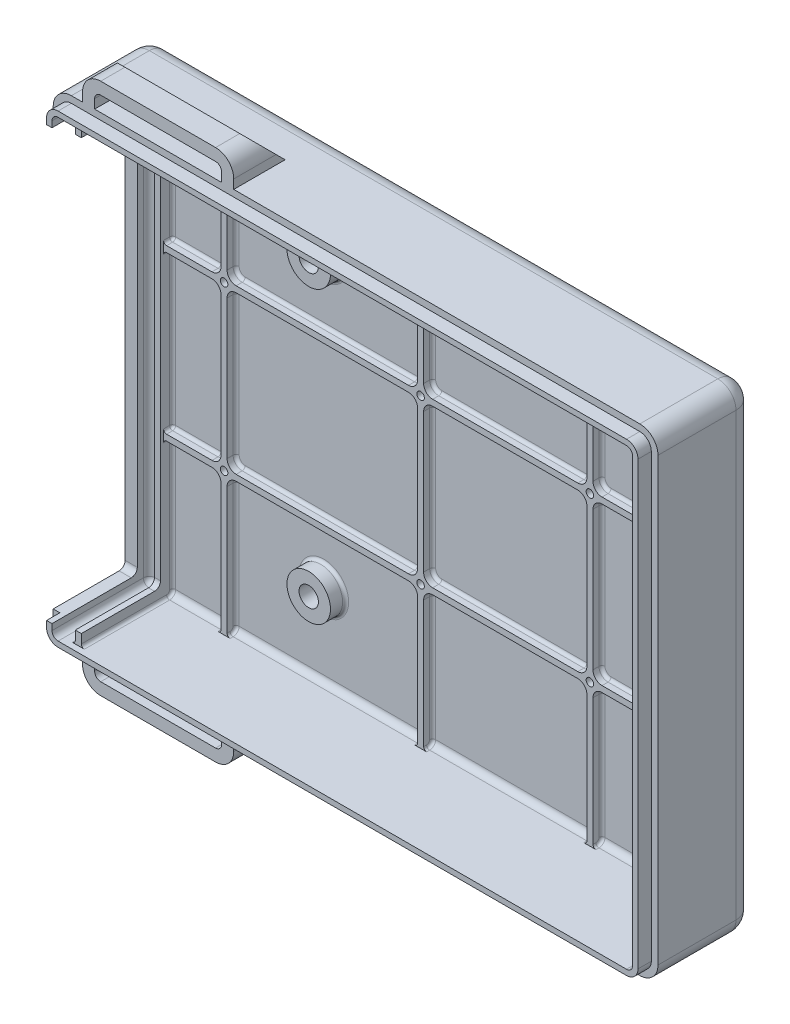
SolidWorks part; units mm, degrees
ref_plane "前视基准面" through (0, 0, 0) normal (0, 0, 1) x (1, 0, 0)
ref_plane "上视基准面" through (0, 0, 0) normal (0, 1, 0) x (1, 0, 0)
ref_plane "右视基准面" through (0, 0, 0) normal (1, 0, 0) x (0, 0, -1)
sketch "草图1" plane through (0, 0, 0) normal (0, 0, 1) x (1, 0, 0)
  line L1 (0, 0) -> (96, 0)
  line L2 (0, 0) -> (0, 75)
  line L3 (0, 75) -> (96, 75)
  line L4 (96, 0) -> (96, 75)
  dimension "D1" = 96
  dimension "D2" = 75
extrude "凸台-拉伸1" add sketch "草图1" along normal blind 2
sketch "草图2" plane through (0, 0, 0) normal (0, 0, 1) x (1, 0, 0)
  line L20 (-2, 77) -> (98, 77)
  line L21 (-2, 77) -> (-2, -2)
  line L22 (-2, -2) -> (98, -2)
  line L23 (98, 77) -> (98, -2)
  line L24 (0, 75) -> (96, 75)
  line L25 (0, 75) -> (0, 0)
  line L26 (0, 0) -> (96, 0)
  line L27 (96, 75) -> (96, 0)
  dimension "D1" = 2
  dimension "D2" = 2
  dimension "D3" = 2
  dimension "D4" = 2
extrude "凸台-拉伸2" add sketch "草图2" along normal blind 18.1
sketch "草图3" plane through (0, 0, 18.1) normal (0, 0, 1) x (1, 0, 0)
  line L0 (0, 0) -> (96, 0) construction
  line L1 (-0.9, 75.9) -> (96.9, 75.9)
  line L2 (-0.9, 75.9) -> (-0.9, -0.9)
  line L3 (-0.9, -0.9) -> (96.9, -0.9)
  line L4 (96.9, 75.9) -> (96.9, -0.9)
  line L5 (-2, 77) -> (98, 77)
  line L6 (-2, 77) -> (-2, -2)
  line L7 (-2, -2) -> (98, -2)
  line L8 (98, 77) -> (98, -2)
  line L9 (96, 0) -> (96, 75) construction
  line L10 (96, 75) -> (0, 75) construction
  line L11 (0, 75) -> (0, 0) construction
  dimension "D1" = 0.9
  dimension "D2" = 0.9
  dimension "D3" = 0.9
  dimension "D4" = 0.9
extrude "切除-拉伸1" cut sketch "草图3" against normal blind 2.2
fillet "圆角1" radius 1 8 edges at (96, 0, 10.05) (48, 0, 2) (96, 37.5, 2) (48, 75, 2) (96, 75, 10.05) (0, 0, 10.05) (0, 75, 10.05) (0, 37.5, 2)
fillet "圆角2" radius 3 8 edges at (98, -2, 7.95) (48, -2, 0) (48, 77, 0) (98, 37.5, 0) (98, 77, 7.95) (-2, 77, 7.95) (-2, -2, 7.95) (-2, 37.5, 0)
fillet "圆角5" radius 1.9 4 edges at (96.9, -0.9, 17) (96.9, 75.9, 17) (-0.9, 75.9, 17) (-0.9, -0.9, 17)
sketch "草图4" plane through (0, 0, 2) normal (0, 0, 1) x (1, 0, 0)
  line L0 (1, 0) -> (95, 0) construction
  line L1 (48, 75) -> (48, 0) construction
  line L2 (0, 75) -> (96, 75) construction
  line L3 (0, 0) -> (96, 0) construction
  point P0 (3.85, 5)
  point P7 (2.85, 5)
  point P11 (48, 37.5)
  dimension "D1" = 3.85
  dimension "D2" = 5
  dimension "D3" = 2.85
  dimension "D4" = 5
ref_plane "基准面1" through (3.85, 0, 0) normal (1, 0, 0) x (0, 0, -1)
ref_plane "基准面2" through (0, 5, 0) normal (0, 1, 0) x (1, 0, 0)
sketch "草图8" plane through (3.85, 0, 0) normal (1, 0, 0) x (0, 0, -1)
  line L0 (8.305, 5) -> (-8.305, 5) construction
  point P0 (-4.5, 5)
  dimension "D1" = 2.5
ref_plane "基准面3" through (0, 0, 4.5) normal (0, 0, 1) x (1, 0, 0)
ref_plane "基准面4" through (2.85, 0, 0) normal (1, 0, 0) x (0, 0, -1)
sketch "草图11" plane through (2.85, 0, 0) normal (1, 0, 0) x (0, 0, -1)
  line L0 (0, 0) -> (0, 75) construction
  line L1 (-17.1, 75) -> (-2, 75)
  line L2 (-17.1, 75) -> (-17.1, 0)
  line L3 (-17.1, 0) -> (-2, 0)
  line L4 (-2, 75) -> (-2, 0)
  line L5 (-15.9, -2) -> (-3, -2) construction
  line L7 (-3, 77) -> (-15.9, 77) construction
  dimension "D2" = 2
  dimension "D3" = 2
  dimension "D4" = 15.1
extrude "凸台-拉伸3" add sketch "草图11" along normal blind 1
sketch "草图9" plane through (0, 0, 0) normal (1, 0, 0) x (0, 0, -1)
  line L0 (-18.1, 75) -> (-3, 75) construction
  line L1 (-4, 73) -> (-18.1, 73)
  line L2 (-4, 73) -> (-4, 2)
  line L3 (-4, 2) -> (-18.1, 2)
  line L4 (-18.1, 73) -> (-18.1, 2)
  line L5 (-3, 0) -> (-18.1, 0) construction
  dimension "D1" = 2
  dimension "D2" = 2
  dimension "D3" = 2
  dimension "D4" = 14.1
extrude "切除-拉伸3" cut sketch "草图9" against normal through all and the other way up to surface (3.85 mm away) other way up to face at (3.85, 37.5, 7.2976)
fillet "圆角8" radius 1 4 edges at (-1, 2, 4) (3.35, 2, 4) (3.35, 73, 4) (-1, 73, 4)
fillet "圆角9" radius 0.5 10 edges at (2.85, 0, 10.05) (2.85, 0.2929, 2.2929) (2.85, 37.5, 2) (2.85, 74.7071, 2.2929) (3.85, 0, 10.05) (3.85, 0.2929, 2.2929) (3.85, 37.5, 2) (3.85, 74.7071, 2.2929) (2.85, 75, 10.05) (3.85, 75, 10.05)
sketch "草图14" plane through (0, 0, 2) normal (0, 0, 1) x (1, 0, 0)
  circle A0 centre (90.85, 13.5) radius 3.4
  circle A1 centre (90.85, 61.5) radius 3.4
  circle A2 centre (28.85, 13.5) radius 3.6
  circle A3 centre (28.85, 61.5) radius 3.6
  dimension "D1" = 6.8
  dimension "D2" = 6.8
  dimension "D7" = 7.2
  dimension "D8" = 7.2
  dimension "D3" = 88
  dimension "D4" = 56.5
  dimension "D5" = 88
  dimension "D6" = 8.5
  dimension "D9" = 26
  dimension "D10" = 8.5
  dimension "D11" = 26
  dimension "D12" = 56.5
extrude "凸台-拉伸4" add sketch "草图14" along normal blind 2.5
sketch "草图15" plane through (0, 0, 4.5) normal (0, 0, 1) x (1, 0, 0)
  circle A0 centre (28.85, 61.5) radius 1.6
  circle A1 centre (28.85, 13.5) radius 1.6
  dimension "D1" = 3.2
  dimension "D2" = 3.2
extrude "切除-拉伸4" cut sketch "草图15" against normal through all
sketch "草图16" plane through (0, 0, 4.5) normal (0, 0, 1) x (1, 0, 0)
  circle A0 centre (90.85, 61.5) radius 1.6
  circle A1 centre (90.85, 13.5) radius 1.6
  dimension "D1" = 3.2
  dimension "D2" = 3.2
extrude "切除-拉伸5" cut sketch "草图16" against normal through all
fillet "圆角10" radius 0.5 4 edges at (25.25, 13.5, 2) (25.25, 61.5, 2) (87.45, 13.5, 2) (87.45, 61.5, 2)
chamfer "倒角2" distance 1.5 angle 45 4 edges at (30.45, 13.5, 0) (30.45, 61.5, 0) (92.45, 61.5, 0) (92.45, 13.5, 0)
sketch "草图17" plane through (0, 0, 2) normal (0, 0, 1) x (1, 0, 0)
  line L0 (3.85, -8.305) -> (3.85, 8.305) construction
  line L1 (3.85, 51) -> (13.35, 51)
  line L2 (3.85, 51) -> (3.85, 50)
  line L3 (3.85, 50) -> (13.35, 50)
  line L4 (96, 51) -> (96, 50)
  line L5 (96, 0) -> (96, 75) construction
  line L6 (0, 75) -> (96, 75) construction
  line L7 (13.35, 75) -> (14.35, 75)
  line L8 (13.35, 75) -> (13.35, 51)
  line L9 (13.35, 0) -> (14.35, 0)
  line L10 (14.35, 75) -> (14.35, 51)
  line L11 (0, 0) -> (96, 0) construction
  line L12 (14.35, 51) -> (45.85, 51)
  line L13 (45.85, 75) -> (46.85, 75)
  line L14 (45.85, 75) -> (45.85, 51)
  line L15 (45.85, 0) -> (46.85, 0)
  line L16 (46.85, 75) -> (46.85, 51)
  line L17 (73.85, 75) -> (74.85, 75)
  line L18 (73.85, 75) -> (73.85, 51)
  line L19 (73.85, 0) -> (74.85, 0)
  line L20 (74.85, 75) -> (74.85, 51)
  line L21 (3.85, 24) -> (13.35, 24)
  line L22 (3.85, 24) -> (3.85, 23)
  line L23 (3.85, 23) -> (13.35, 23)
  line L24 (96, 24) -> (96, 23)
  line L25 (14.35, 50) -> (45.85, 50)
  line L26 (14.35, 50) -> (14.35, 24)
  line L27 (13.35, 50) -> (13.35, 24)
  line L28 (46.85, 51) -> (73.85, 51)
  line L29 (46.85, 50) -> (73.85, 50)
  line L30 (46.85, 50) -> (46.85, 24)
  line L31 (45.85, 50) -> (45.85, 24)
  line L32 (74.85, 51) -> (96, 51)
  line L33 (74.85, 50) -> (96, 50)
  line L34 (73.85, 50) -> (73.85, 24)
  line L35 (74.85, 24) -> (96, 24)
  line L36 (74.85, 23) -> (96, 23)
  line L37 (74.85, 23) -> (74.85, 0)
  line L38 (73.85, 23) -> (73.85, 0)
  line L39 (46.85, 24) -> (73.85, 24)
  line L40 (46.85, 23) -> (73.85, 23)
  line L41 (46.85, 23) -> (46.85, 0)
  line L42 (45.85, 23) -> (45.85, 0)
  line L43 (14.35, 24) -> (45.85, 24)
  line L44 (14.35, 23) -> (45.85, 23)
  line L45 (14.35, 23) -> (14.35, 0)
  line L46 (13.35, 23) -> (13.35, 0)
  line L47 (74.85, 50) -> (74.85, 24)
  dimension "D6" = 24
  dimension "D7" = 23
  dimension "D8" = 9.5
  dimension "D9" = 42
  dimension "D10" = 70
extrude "凸台-拉伸5" add sketch "草图17" along normal blind 1.5
fillet "圆角11" radius 1.5 24 edges at (74.85, 23, 2.75) (73.85, 23, 2.75) (46.85, 23, 2.75) (45.85, 23, 2.75) (13.35, 23, 2.75) (14.35, 23, 2.75) (13.35, 51, 2.75) (73.85, 51, 2.75) (74.85, 51, 2.75) (46.85, 51, 2.75) (45.85, 51, 2.75) (14.35, 51, 2.75) (13.35, 24, 2.75) (13.35, 50, 2.75) (74.85, 24, 2.75) (74.85, 50, 2.75) (73.85, 24, 2.75) (73.85, 50, 2.75) (46.85, 24, 2.75) (46.85, 50, 2.75) (45.85, 24, 2.75) (45.85, 50, 2.75) (14.35, 24, 2.75) (14.35, 50, 2.75)
sketch "草图18" plane through (0, 0, 3.5) normal (0, 0, 1) x (1, 0, 0)
  line L0 (11.85, 50) -> (15.85, 51) construction
  line L1 (44.35, 50) -> (48.35, 51) construction
  line L2 (72.35, 50) -> (76.35, 51) construction
  line L3 (11.85, 23) -> (15.85, 24) construction
  line L4 (44.35, 23) -> (48.35, 24) construction
  line L5 (72.35, 23) -> (76.35, 24) construction
  arc A0 (45.85, 48.5) -> (44.35, 50) centre (44.35, 48.5) ccw construction
  arc A1 (13.35, 21.5) -> (11.85, 23) centre (11.85, 21.5) ccw construction
  arc A2 (13.35, 21.5) -> (11.85, 23) centre (11.85, 21.5) ccw construction
  arc A3 (73.85, 21.5) -> (72.35, 23) centre (72.35, 21.5) ccw construction
  arc A4 (73.85, 21.5) -> (72.35, 23) centre (72.35, 21.5) ccw construction
  circle A5 centre (13.85, 50.5) radius 0.625
  circle A6 centre (46.35, 50.5) radius 0.625
  circle A7 centre (74.35, 50.5) radius 0.625
  circle A8 centre (74.35, 23.5) radius 0.625
  circle A9 centre (46.35, 23.5) radius 0.625
  circle A10 centre (13.85, 23.5) radius 0.625
  dimension "D1" = 1.25
  dimension "D2" = 1.25
  dimension "D3" = 1.25
  dimension "D4" = 1.25
  dimension "D5" = 1.25
  dimension "D6" = 1.25
extrude "切除-拉伸6" cut sketch "草图18" against normal blind 1.5
fillet "圆角12" radius 0.5 104 edges at (74.85, 0, 3.25) (74.85, 0.2929, 2.2929) (96, 23, 3.25) (95.7071, 23, 2.2929) (85.675, 23, 2) (75.2893, 22.5607, 2) (46.85, 0, 3.25) (46.85, 0.2929, 2.2929) (46.85, 11.25, 2) (47.2893, 22.5607, 2) (73.85, 0, 3.25) (73.85, 0.2929, 2.2929) (73.85, 11.25, 2) (73.4107, 22.5607, 2) (14.35, 0, 3.25) (14.35, 0.2929, 2.2929) (14.35, 11.25, 2) (14.7893, 22.5607, 2) (45.85, 0, 3.25) (45.85, 0.2929, 2.2929) (45.85, 11.25, 2) (45.4107, 22.5607, 2) (3.85, 23, 3) (3.9964, 23, 2.1464) (13.35, 0, 3.25) (13.35, 0.2929, 2.2929) (13.35, 11.25, 2) (12.9107, 22.5607, 2) (96, 24, 3.25) (95.7071, 24, 2.2929) (85.675, 24, 2) (75.2893, 24.4393, 2) (74.85, 37, 2) (75.2893, 49.5607, 2) (96, 50, 3.25) (95.7071, 50, 2.2929) (96, 51, 3.25) (95.7071, 51, 2.2929) (85.675, 51, 2) (75.2893, 51.4393, 2) (74.85, 75, 3.25) (74.85, 74.7071, 2.2929) (60.35, 50, 2) (73.4107, 49.5607, 2) (73.85, 37, 2) (73.4107, 24.4393, 2) (60.35, 24, 2) (47.2893, 24.4393, 2) (46.85, 37, 2) (73.85, 75, 3.25) (73.85, 74.7071, 2.2929) (73.85, 63.25, 2) (73.4107, 51.4393, 2) (60.35, 51, 2) (47.2893, 51.4393, 2) (46.85, 75, 3.25) (46.85, 74.7071, 2.2929) (45.4107, 49.5607, 2) (45.85, 37, 2) (45.4107, 24.4393, 2) (30.1, 24, 2) (14.7893, 24.4393, 2) (14.35, 37, 2) (14.7893, 49.5607, 2) (3.85, 50, 3) (3.9964, 50, 2.1464) (3.85, 24, 3) (3.9964, 24, 2.1464) (8.1, 24, 2) (12.9107, 24.4393, 2) (13.35, 37, 2) (12.9107, 49.5607, 2) (13.35, 75, 3.25) (13.35, 74.7071, 2.2929) (3.85, 51, 3) (3.9964, 51, 2.1464) (8.1, 51, 2) (12.9107, 51.4393, 2) (45.85, 75, 3.25) (45.85, 74.7071, 2.2929) (45.85, 63.25, 2) (45.4107, 51.4393, 2) (30.1, 51, 2) (14.7893, 51.4393, 2) (14.35, 75, 3.25) (14.35, 74.7071, 2.2929) (74.85, 11.25, 2) (60.35, 23, 2) (30.1, 23, 2) (8.1, 23, 2) (85.675, 50, 2) (74.85, 63.25, 2) (47.2893, 49.5607, 2) (46.85, 63.25, 2) (30.1, 50, 2) (8.1, 50, 2) (13.35, 63.25, 2) (14.35, 63.25, 2) (14.475, 50.5, 2) (46.975, 50.5, 2) (74.975, 50.5, 2) (74.975, 23.5, 2) (46.975, 23.5, 2) (14.475, 23.5, 2)
sketch "草图19" plane through (0, 0, 15.9) normal (0, 0, 1) x (1, 0, 0)
  line L0 (95, 77) -> (1, 77) construction
  line L1 (2.85, 77) -> (4.85, 77)
  line L2 (2.85, 77) -> (2.85, 81.5)
  line L3 (2.85, 81.5) -> (27.85, 81.5)
  line L4 (27.85, 77) -> (27.85, 81.5)
  line L5 (2.85, -8.305) -> (2.85, 8.305) construction
  line L7 (4.85, 77) -> (4.85, 79.5)
  line L8 (4.85, 79.5) -> (25.85, 79.5)
  line L9 (25.85, 77) -> (25.85, 79.5)
  line L10 (25.85, 77) -> (27.85, 77)
  dimension "D1" = 21
  dimension "D2" = 2
  dimension "D3" = 2
  dimension "D4" = 2
  dimension "D5" = 2.5
  dimension "D6" = 0
extrude "凸台-拉伸6" add sketch "草图19" against normal blind 4
ref_plane "基准面5" through (0, 37.5, 0) normal (0, -1, 0) x (-1, 0, 0)
mirror "镜向1" about plane through (0, 37.5, 0) normal (0, -1, 0) of "凸台-拉伸6"
chamfer "倒角3" distance 4.5 angle 45 2 edges at (26.85, -2, 11.9) (3.85, 77, 11.9)
fillet "圆角13" radius 1 4 edges at (25.85, 79.5, 12.9) (4.85, 79.5, 12.9) (25.85, -4.5, 12.9) (4.85, -4.5, 12.9)
fillet "圆角14" radius 3 4 edges at (2.85, -6.5, 13.9) (27.85, -6.5, 13.9) (27.85, 81.5, 13.9) (2.85, 81.5, 13.9)
sketch "草图20" plane through (0, 0, 0) normal (0, 0, -1) x (-1, 0, 0)
  line L0 (-8.305, 37.5) -> (8.305, 37.5) construction
  line L1 (-80.9912, 62.75) -> (-50.4912, 62.75)
  line L2 (-80.9912, 62.75) -> (-80.9912, 12.25)
  line L3 (-80.9912, 12.25) -> (-50.4912, 12.25)
  line L4 (-50.4912, 62.75) -> (-50.4912, 12.25)
  line L5 (-80.9912, 62.75) -> (-50.4912, 12.25) construction
  line L6 (-80.9912, 12.25) -> (-50.4912, 62.75) construction
  point P0 (-65.7412, 37.5)
  dimension "D1" = 30.5
  dimension "D2" = 50.5
extrude "切除-拉伸7" cut sketch "草图20" against normal blind 0.3
sketch "草图21" plane through (0, 0, 0) normal (0, 0, -1) x (-1, 0, 0)
  line L0 (0.9219, 74) -> (-95, 1) construction
  line L1 (-1, 74) -> (-95, 74) construction
  line L2 (-48, 75) -> (-48, 0) construction
  line L3 (-93.3155, 3.7445) -> (-2.6845, 3.7445) construction
  line L4 (-93.3155, 3.7445) -> (-93.3155, 71.2555) construction
  line L5 (-93.3155, 71.2555) -> (-2.6845, 71.2555) construction
  line L6 (-2.6845, 3.7445) -> (-2.6845, 71.2555) construction
  line L7 (-93.3155, 3.7445) -> (-2.6845, 71.2555) construction
  line L8 (-93.3155, 71.2555) -> (-2.6845, 3.7445) construction
  circle A0 centre (-93.3155, 71.2555) radius 0.75
  circle A1 centre (-2.6845, 71.2555) radius 0.75
  circle A2 centre (-93.3155, 3.7445) radius 0.75
  circle A3 centre (-2.6845, 3.7445) radius 0.75
  point P5 (-48, 37.5)
  point P6 (-48, 37.5)
  dimension "D1" = 1.5
  dimension "D2" = 1.5
  dimension "D3" = 1.5
  dimension "D4" = 1.5
extrude "凸台-拉伸7" add sketch "草图21" along normal blind 0.75
fillet "圆角15" radius 0.75 4 edges at (92.5655, 3.7445, -0.75) (1.9345, 3.7445, -0.75) (1.9345, 71.2555, -0.75) (92.5655, 71.2555, -0.75)
equation "\"dim.x.base_internal\" = 96"
equation "\"dim.y.base_internal\"= 75"
equation "\"thickness.wall.side\"= 2"
equation "\"thickness.rib\"= \"thickness.wall.side\" * 0.5"
equation "\"thickness.gasset\"= \"thickness.wall.side\" * 0.5"
equation "\"dim.y.xlr1_to_datum\"= 13"
equation "\"dim.y.xlr2_to_datum\"= 40"
equation "\"dim.z.board_to_base\"=2.5"
equation "\"dim.z.board_thickness\"= 1.6"
equation "\"D1@草图1\"=\"dim.x.base_internal\""
equation "\"D2@草图1\"=\"dim.y.base_internal\""
equation "\"D1@凸台-拉伸1\"=\"thickness.wall.side\""
equation "\"dim.z.xlr_opening_to_board\"= 12.5"
equation "\"dim.z.base_internal\"= 16.1"
equation "\"dim.z.base_external\"= \"dim.z.base_internal\" + \"thickness.wall.side\""
equation "\"D1@草图2\"=\"thickness.wall.side\""
equation "\"D2@草图2\"=\"thickness.wall.side\""
equation "\"D3@草图2\"=\"thickness.wall.side\""
equation "\"D4@草图2\"=\"thickness.wall.side\""
equation "\"D1@凸台-拉伸2\"=\"dim.z.base_external\""
equation "\"thickness.mating.side\"= ( \"thickness.wall.side\" / 2 ) - 0.1"
equation "\"D3@草图3\"=\"thickness.mating.side\""
equation "\"D1@草图3\"=\"thickness.mating.side\""
equation "\"D2@草图3\"=\"thickness.mating.side\""
equation "\"D4@草图3\"=\"thickness.mating.side\""
equation "\"dim.cut.mating_cut\"= \"thickness.wall.side\" * 1 + 0.2"
equation "\"D1@切除-拉伸1\"=\"dim.cut.mating_cut\""
equation "\"dim.r.side_internal\"= \"thickness.wall.side\" * 0.5"
equation "\"dim.r.side_external\"= \"thickness.wall.side\" * 1.5"
equation "\"D1@圆角1\"=\"dim.r.side_internal\""
equation "\"D1@圆角2\"=\"dim.r.side_external\""
equation "\"dim.r.mating_side_external\"= \"dim.r.side_internal\" + \"thickness.mating.side\""
equation "\"D1@圆角5\"=\"dim.r.mating_side_external\""
equation "\"mea.x.board_length\"= 65"
equation "\"mea.y.board_width\"= 65"
equation "\"dim.y.board_clearance\"= 5"
equation "\"dim.z.xlr_lower_drill_to_board\"= 2.75"
equation "\"dim.z.xlr_up_drill_to_board\"= \"dim.z.xlr_lower_drill_to_board\" + 19.8"
equation "\"dim.d.xlr_opening\"= 22.2"
equation "\"dim.y.xlr_drill_to_center\"= 19.8 / 2"
equation "\"dim.d.xlr_drill\"= 3.2"
equation "\"dim.y.switch_opening_width\"= 3.3"
equation "\"dim.z.switch_opening_height\"= 7"
equation "\"dim.r.switch_opening_chamfer\"= \"dim.y.switch_opening_width\" / 2"
equation "\"dim.z.switch_opening_to_board\"= 6.66"
equation "\"dim.y.switch_opening_to_datum\"= 58"
equation "\"D2@草图4\"=\"dim.y.board_clearance\""
equation "\"D1@草图8\"=\"dim.z.board_to_base\""
equation "\"dim.y.front_opening_side\"= 2"
equation "\"dim.z.front_opening_bottom\"= 2"
equation "\"D1@草图9\"=\"dim.y.front_opening_side\""
equation "\"D2@草图9\"=\"dim.y.front_opening_side\""
equation "\"D4@草图9\"=\"dim.z.base_internal\"-\"dim.z.front_opening_bottom\""
equation "\"D3@草图9\"=\"dim.z.front_opening_bottom\""
equation "\"dim.x.front_opening_slot\"= 2.85"
equation "\"D3@草图4\"=\"dim.x.front_opening_slot\""
equation "\"D1@草图4\"=\"dim.x.front_opening_slot\"+ \"dim.x.thickness_front_opening_rib\""
equation "\"D1@草图11\"=\"thickness.wall.side\""
equation "\"D2@草图11\"=\"thickness.wall.side\""
equation "\"D3@草图11\"=\"thickness.wall.side\""
equation "\"D4@草图11\"=\"dim.z.base_internal\" - 1"
equation "\"dim.x.thickness_front_opening_rib\"= 1"
equation "\"D1@凸台-拉伸3\"=\"dim.x.thickness_front_opening_rib\""
equation "\"D1@圆角8\"=\"dim.r.side_internal\""
equation "\"D1@圆角9\"=\"dim.r.rib_chamfer\""
equation "\"dim.r.rib_chamfer\"= 0.5"
equation "\"dim.r.gussets_chamfer\"= 0.5"
equation "\"dim.d.boss_short_drill\"=2.8"
equation "\"dim.d.boss_short\"= \"dim.d.boss_short_drill\" + 2 * \"thickness.wall.side\""
equation "\"dim.d.boss_long_drill\"= 2.2"
equation "\"dim.d.boss_long\"= \"dim.d.boss_long_drill\" * 3"
equation "\"dim.z.boss_long_height\"= 20"
equation "\"dim.z.boss_long_depth\"= \"dim.z.boss_long_height\" + 0.35 * \"thickness.wall.side\""
equation "\"dim.r.boss_short\"= 0.5"
equation "\"dim.r.boss_long\"= 1"
equation "\"dim.d.boss_long_chamfer\"= 0.5"
equation "\"D1@草图14\"=\"dim.d.boss_short\""
equation "\"D2@草图14\"=\"dim.d.boss_short\""
equation "\"dim.d.drill_st3\"= 3.20mm"
equation "\"dim.d.boss_short_st\"= \"dim.d.drill_st3\" + 2 * \"thickness.wall.side\""
equation "\"D7@草图14\"=\"dim.d.boss_short_st\""
equation "\"D8@草图14\"=\"dim.d.boss_short_st\""
equation "\"D1@凸台-拉伸4\"=\"dim.z.board_to_base\""
equation "\"D1@草图15\"=\"dim.d.drill_st3\""
equation "\"D2@草图15\"=\"dim.d.drill_st3\""
equation "\"D1@草图16\"=\"dim.d.drill_st3\""
equation "\"D2@草图16\"=\"dim.d.drill_st3\""
equation "\"D1\"= \"dim.z.boss_short_depth\""
equation "\"D1@圆角10\"=\"dim.r.boss_short\""
equation "\"dim.d.chamfer_external_st3\"= 1.5"
equation "\"D1@倒角2\"=\"dim.d.chamfer_external_st3\""
equation "\"dim.d.chamfer_external_m2.5\"= 1.5"
equation "\"D4@草图4\"=\"dim.y.board_clearance\""
equation "\"D1@草图17\"=\"thickness.rib\""
equation "\"D2@草图17\"=\"thickness.rib\""
equation "\"D3@草图17\"=\"thickness.rib\""
equation "\"D4@草图17\"=\"thickness.rib\""
equation "\"D5@草图17\"=\"thickness.rib\""
equation "\"dim.z.rib_height\"= 1.5"
equation "\"dim.d.rib_coring\"= 1.25"
equation "\"D1@草图18\"=\"dim.d.rib_coring\""
equation "\"D2@草图18\"=\"dim.d.rib_coring\""
equation "\"D3@草图18\"=\"dim.d.rib_coring\""
equation "\"D4@草图18\"=\"dim.d.rib_coring\""
equation "\"D5@草图18\"=\"dim.d.rib_coring\""
equation "\"D6@草图18\"=\"dim.d.rib_coring\""
equation "\"D1@切除-拉伸6\"=\"dim.z.rib_height\""
equation "\"D1@凸台-拉伸5\"=\"dim.z.rib_height\""
equation "\"D1@圆角12\"=\"dim.r.rib_chamfer\""
